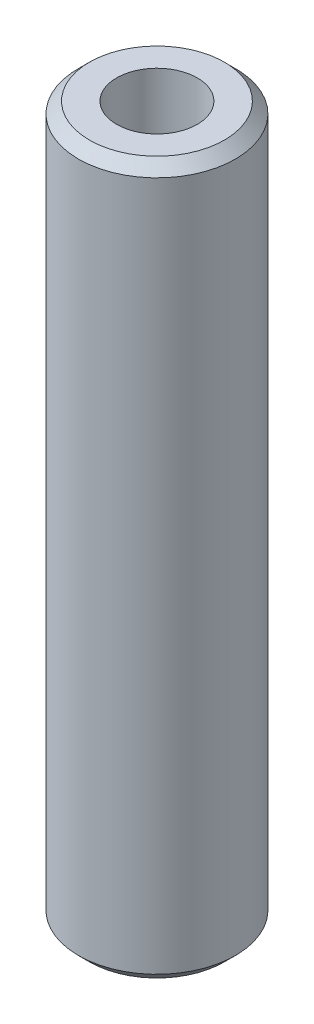
SolidWorks part; units mm, degrees
ref_plane "Front Plane" through (0, 0, 0) normal (0, 0, 1) x (1, 0, 0)
ref_plane "Top Plane" through (0, 0, 0) normal (0, 1, 0) x (1, 0, 0)
ref_plane "Right Plane" through (0, 0, 0) normal (1, 0, 0) x (0, 0, -1)
sketch "Sketch1" plane through (0, 0, 0) normal (0, 1, 0) x (1, 0, 0)
  circle A0 centre (0, 0) radius 15
  dimension "SHAFT_OD" = 30
extrude "Boss-Extrude1" add sketch "Sketch1" along normal blind 136.0175
sketch "Sketch2" plane through (0, 0, 0) normal (0, 1, 0) x (1, 0, 0)
  circle A0 centre (0, 0) radius 7.7052
  dimension "BORE_D" = 15.4103
extrude "Cut-Extrude1" cut sketch "Sketch2" along normal through all
chamfer "Chamfer1" distance 2.0984 angle 45 2 edges at (0, 136.0175, 15) (0, 0, 15)
